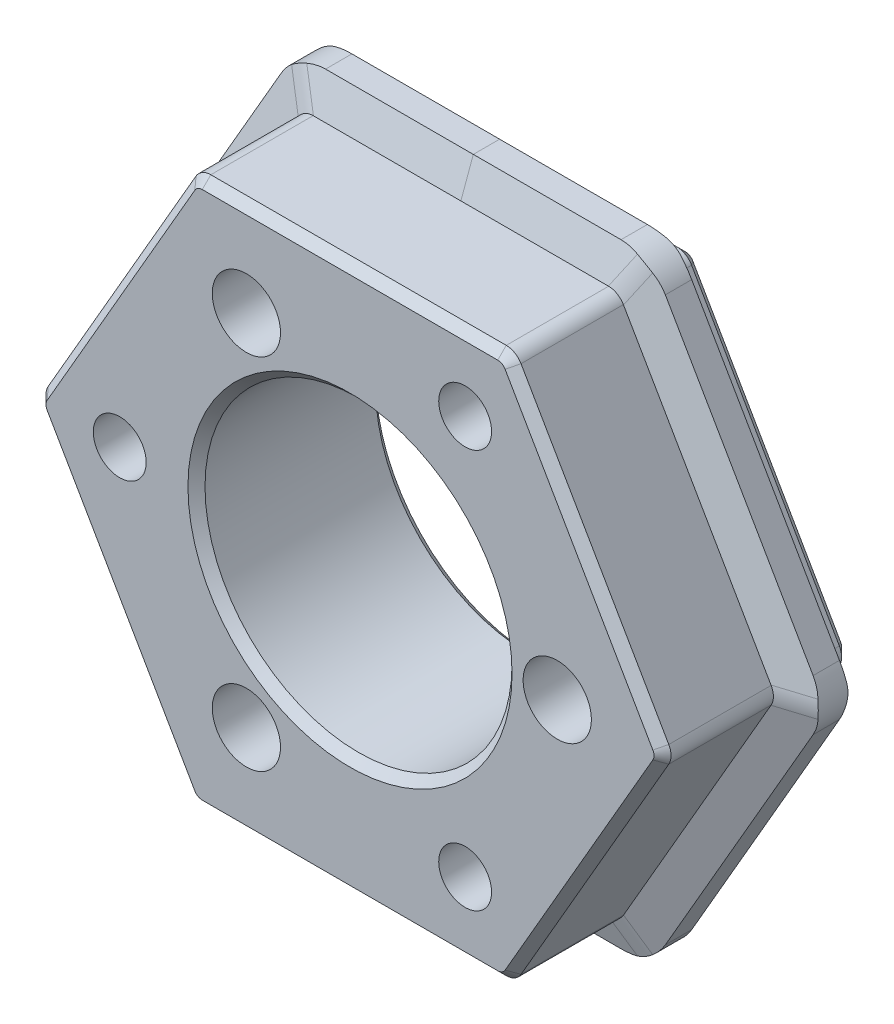
SolidWorks part; units mm, degrees
material "6061 合金"
ref_plane "前视基准面" through (0, 0, 0) normal (0, 0, 1) x (1, 0, 0)
ref_plane "上视基准面" through (0, 0, 0) normal (0, 1, 0) x (1, 0, 0)
ref_plane "右视基准面" through (0, 0, 0) normal (1, 0, 0) x (0, 0, -1)
other "Configuration Table"
sketch "草图2" plane through (0, 0, 0) normal (0, 0, 1) x (1, 0, 0)
  line L1 (9.2376, 16) -> (-9.2376, 16)
  line L2 (-9.2376, 16) -> (-18.4752, 0)
  line L3 (-18.4752, 0) -> (-9.2376, -16)
  line L4 (-9.2376, -16) -> (9.2376, -16)
  line L5 (9.2376, -16) -> (18.4752, 0)
  line L6 (18.4752, 0) -> (9.2376, 16)
  circle A0 centre (0, 0) radius 16 construction
  dimension "D1" = 32
extrude "凸台-拉伸1" add sketch "草图2" along normal mid plane 11
sketch "草图4" plane through (0, 0, -5.5) normal (0, 0, -1) x (-1, 0, 0)
  line L0 (-18.4752, 0) -> (0, 0) construction
  line L1 (0, 0) -> (-6.75, 11.6913) construction
  circle A0 centre (0, 0) radius 13.5
  point P0 (-6.75, 11.6913)
  point P24 (13.5, 0)
  point P25 (-6.75, -11.6913)
  dimension "D1" = 27
  dimension "D2" = 60
  dimension "D3" = 3
hole_wizard "M3 六角圆柱头螺钉的柱形沉头孔1" positions "草图4" profile "草图5" counterbore size "M3" standard "GB" end condition through all
sketch "草图5" plane through (6.75, 11.6913, -5.5) normal (1, 0, 0) x (0, 1, 0)
  line L0 (0, 0) -> (0, 11)
  line L1 (0, 11) -> (1.55, 11)
  line L3 (1.55, 11) -> (1.55, 3.1)
  line L4 (1.55, 3.1) -> (3, 3.1)
  line L5 (3, 3.1) -> (3, 0)
  line L7 (3, 0) -> (0, 0)
  line L11 (0, -6.35) -> (0, 107.95) construction
  dimension "通孔孔直径" = 3.1
  dimension "通孔孔深度" = 11
  dimension "柱形沉头孔直径" = 6
  dimension "柱形沉头孔深度" = 3.1
sketch "草图6" plane through (0, 0, 5.5) normal (0, 0, 1) x (1, 0, 0)
  line L0 (-23.5778, 0) -> (0, 0) construction
  line L1 (0, 0) -> (-6.075, 10.5222) construction
  circle A0 centre (0, 0) radius 12.15
  point P0 (-6.075, 10.5222)
  point P19 (12.15, 0)
  point P20 (-6.075, -10.5222)
  dimension "D1" = 24.3
  dimension "D2" = 60
  dimension "D3" = 3
hole_wizard "Ø4.0mm 暗销孔1" positions "草图6" profile "草图7" hole size "Ø4.0" standard "GB"
sketch "草图7" plane through (-6.075, 10.5222, 5.5) normal (1, 0, 0) x (0, -1, 0)
  line L0 (0, 0) -> (0, 4.2017)
  line L1 (0, 4.2017) -> (2, 3)
  line L2 (2, 3) -> (2, 0)
  line L5 (2, 0) -> (0, 0)
  line L10 (0, 4.2017) -> (-2, 3) construction
  line L11 (0, -6.35) -> (0, 107.95) construction
  dimension "孔直径" = 4
  dimension "孔深度" = 3
  dimension "导头角度" = 118
sketch "草图8" plane through (0, 0, 5.5) normal (0, 0, 1) x (1, 0, 0)
  circle A0 centre (0, 0) radius 9
  dimension "D1" = 18
extrude "切除-拉伸1" cut sketch "草图8" against normal through all
ref_plane "基准面1" through (0, 0, -2.5) normal (0, 0, -1) x (-1, 0, 0)
sketch "草图10" plane through (0, 0, -2.5) normal (0, 0, -1) x (-1, 0, 0)
  line L6 (-9.2376, 16) -> (-18.4752, 0)
  line L7 (-18.4752, 0) -> (-9.2376, -16)
  line L8 (-9.2376, -16) -> (9.2376, -16)
  line L9 (9.2376, -16) -> (18.4752, 0)
  line L10 (18.4752, 0) -> (9.2376, 16)
  line L11 (9.2376, 16) -> (-9.2376, 16)
  line L12 (-9.2376, 16) -> (-18.4752, 0)
  line L13 (-18.4752, 0) -> (-9.2376, -16)
  line L14 (-9.2376, -16) -> (9.2376, -16)
  line L15 (9.2376, -16) -> (18.4752, 0)
  line L16 (18.4752, 0) -> (9.2376, 16)
  line L17 (9.2376, 16) -> (-9.2376, 16)
  dimension "D1" = 0
sketch "草图11" plane through (0, 0, 0) normal (1, 0, 0) x (0, 0, -1)
  line L0 (2.5, 16) -> (2.5, 0) construction
  line L1 (2.5, 16) -> (2.5, -0.3955) construction
  line L2 (1, 16) -> (1.7279, 18)
  line L3 (-5.5, 16) -> (5.5, 16) construction
  line L4 (1.7279, 18) -> (3.2721, 18)
  line L5 (3.2721, 18) -> (4, 16)
  line L6 (4, 16) -> (1, 16)
  dimension "D1" = 2
  dimension "D2" = 40
  dimension "D3" = 3
sweep "扫描1" add profiles "草图11" path "草图10"
fillet "圆角1" radius 3 18 edges at (10.3923, 18, -2.5) (20.7846, 0, -2.5) (10.3923, -18, -2.5) (-10.3923, -18, -2.5) (-20.7846, 0, -2.5) (-10.3923, 18, -2.5) (-9.815, -17, -3.636) (9.815, -17, -3.636) (19.6299, 0, -3.636) (9.815, 17, -3.636) (-9.815, 17, -3.636) (-19.6299, 0, -3.636) (9.815, 17, -1.364) (-9.815, 17, -1.364) (-19.6299, 0, -1.364) (-9.815, -17, -1.364) (9.815, -17, -1.364) (19.6299, 0, -1.364)
fillet "圆角2" radius 1 12 edges at (-9.2376, -16, 2.2265) (9.2376, -16, 2.2265) (18.4752, 0, 2.2265) (9.2376, 16, 2.2265) (-9.2376, 16, 2.2265) (-18.4752, 0, 2.2265) (-18.4752, 0, -4.7265) (-9.2376, -16, -4.7265) (9.2376, -16, -4.7265) (18.4752, 0, -4.7265) (9.2376, 16, -4.7265) (-9.2376, 16, -4.7265)
chamfer "倒角1" distance 0.5 angle 45 26 edges at (9, 0, 5.5) (9, 0, -5.5) (-13.8564, 8, 5.5) (-18.3205, 0, 5.5) (-9.1603, 15.866, 5.5) (-13.8564, -8, 5.5) (0, 16, 5.5) (-9.1603, -15.866, 5.5) (9.1603, 15.866, 5.5) (0, -16, 5.5) (13.8564, 8, 5.5) (9.1603, -15.866, 5.5) (18.3205, 0, 5.5) (13.8564, -8, 5.5) (0, 16, -5.5) (-9.1603, 15.866, -5.5) (9.1603, 15.866, -5.5) (-13.8564, 8, -5.5) (13.8564, 8, -5.5) (-18.3205, 0, -5.5) (18.3205, 0, -5.5) (-13.8564, -8, -5.5) (13.8564, -8, -5.5) (-9.1603, -15.866, -5.5) (9.1603, -15.866, -5.5) (0, -16, -5.5)
